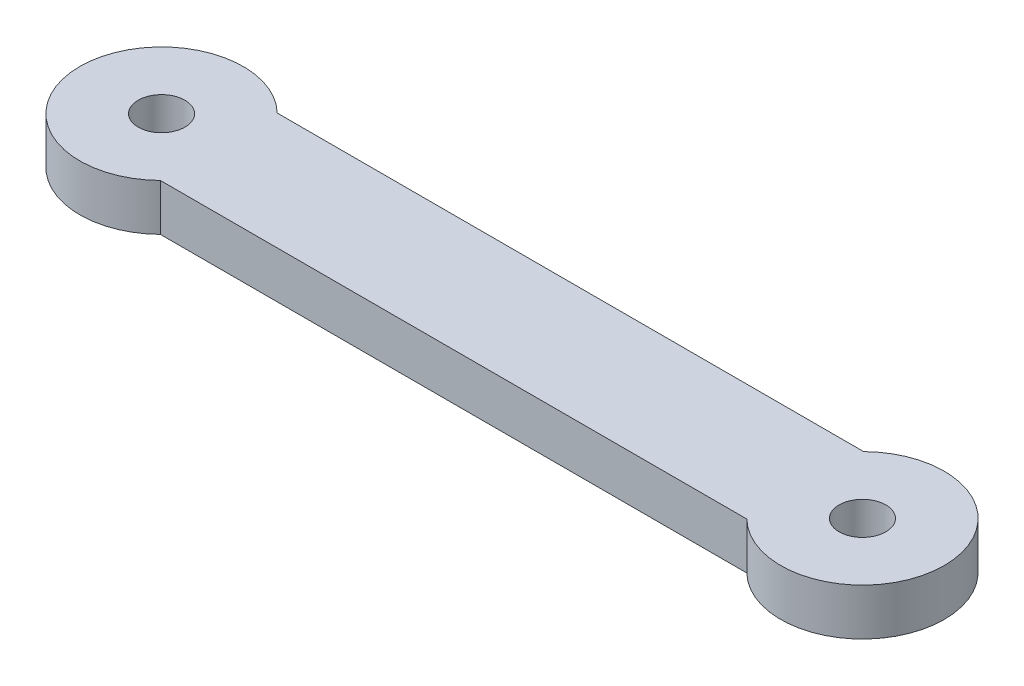
SolidWorks part; units mm, degrees
ref_plane "Alzado" through (0, 0, 0) normal (0, 0, 1) x (1, 0, 0)
ref_plane "Planta" through (0, 0, 0) normal (0, 1, 0) x (1, 0, 0)
ref_plane "Vista lateral" through (0, 0, 0) normal (1, 0, 0) x (0, 0, -1)
sketch "Croquis2" plane through (0, 0, 0) normal (0, 1, 0) x (1, 0, 0)
  line L0 (14.1903, -1.2019) -> (-15.8097, -1.2019) construction
  line L1 (-13.3603, 1.2981) -> (11.7408, 1.2981)
  line L3 (-13.3603, -3.7019) -> (11.7408, -3.7019)
  arc A0 (-13.3603, 1.2981) -> (-13.3603, -3.7019) centre (-15.8097, -1.2019) ccw
  arc A1 (11.7408, -3.7019) -> (11.7408, 1.2981) centre (14.1903, -1.2019) ccw
  circle A2 centre (-15.8097, -1.2019) radius 1
  circle A3 centre (14.1903, -1.2019) radius 1
  point P0 (0, 0)
  dimension "D3" = 2
  dimension "D4" = 7
  dimension "D5" = 7
  dimension "D1" = 5
  dimension "D2" = 30
extrude "Saliente-Extruir1" add sketch "Croquis2" along normal blind 2
